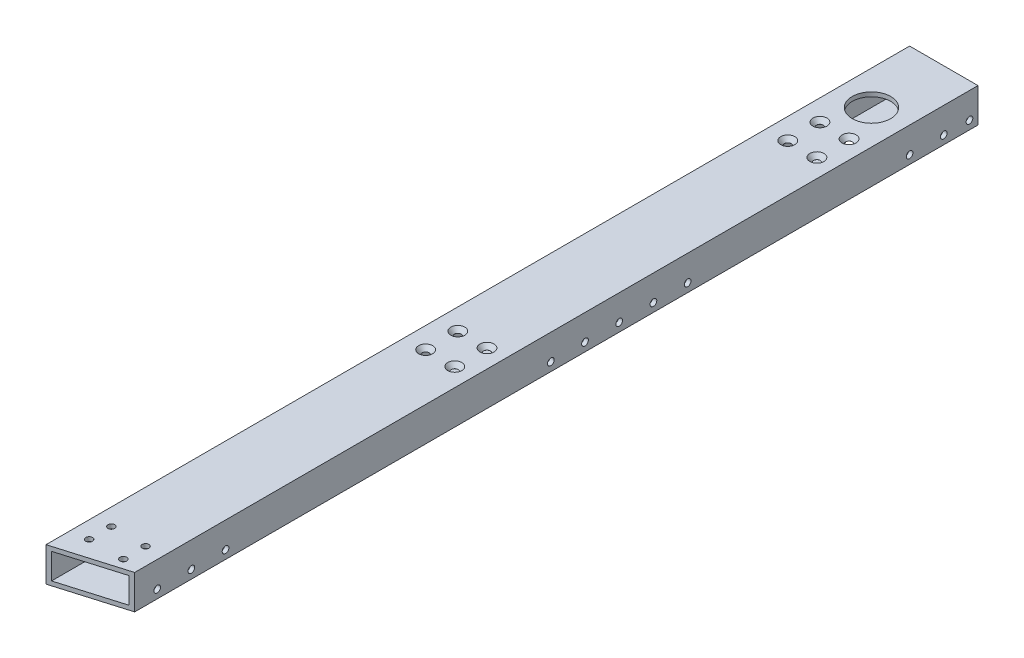
SolidWorks part; units mm, degrees
ref_plane "Front Plane" through (0, 0, 0) normal (0, 0, 1) x (1, 0, 0)
ref_plane "Top Plane" through (0, 0, 0) normal (0, 1, 0) x (1, 0, 0)
ref_plane "Right Plane" through (0, 0, 0) normal (1, 0, 0) x (0, 0, -1)
sketch "Sketch1" plane through (0, 0, 0) normal (0, 0, 1) x (1, 0, 0)
  line L0 (-22.225, 9.525) -> (22.225, 9.525)
  line L2 (-25.4, 12.7) -> (25.4, 12.7)
  line L3 (-25.4, 12.7) -> (-25.4, -12.7)
  line L4 (-25.4, -12.7) -> (25.4, -12.7)
  line L5 (25.4, 12.7) -> (25.4, -12.7)
  line L10 (22.225, 9.525) -> (22.225, -9.525)
  line L11 (-22.225, -9.525) -> (22.225, -9.525)
  line L12 (-22.225, 9.525) -> (-22.225, -9.525)
  point P12 (0, 12.7)
  point P14 (25.4, 0)
  dimension "Wall Thickness" = 3.175
  dimension "Outside Width" = 50.8
  dimension "Outside Height" = 25.4
  dimension "Inside Height" = 19.05
  dimension "Inside Width" = 44.45
sketch "Sketch2" plane through (0, 0, 0) normal (1, 0, 0) x (0, 0, -1)
  line L0 (320.675, 0) -> (-320.675, 0)
  point P4 (0, 0)
  point P7 (-320.675, 0)
  point P10 (320.675, 0)
  dimension "Length" = 641.35
sketch "Sketch3" plane through (0, 0, 0) normal (0, 0, 1) x (1, 0, 0)
  line L21 (25.4, 12.7) -> (-25.4, 12.7)
  line L22 (25.4, -12.7) -> (25.4, 12.7)
  line L23 (-25.4, -12.7) -> (25.4, -12.7)
  line L24 (-25.4, 12.7) -> (-25.4, -12.7)
  line L25 (25.4, 12.7) -> (-25.4, 12.7)
  line L26 (25.4, -12.7) -> (25.4, 12.7)
  line L27 (-25.4, -12.7) -> (25.4, -12.7)
  line L28 (-25.4, 12.7) -> (-25.4, -12.7)
  line L29 (22.225, 9.525) -> (-22.225, 9.525)
  line L30 (22.225, -9.525) -> (22.225, 9.525)
  line L31 (-22.225, -9.525) -> (22.225, -9.525)
  line L32 (-22.225, 9.525) -> (-22.225, -9.525)
  line L33 (22.225, 9.525) -> (-22.225, 9.525)
  line L34 (22.225, -9.525) -> (22.225, 9.525)
  line L35 (-22.225, -9.525) -> (22.225, -9.525)
  line L36 (-22.225, 9.525) -> (-22.225, -9.525)
  dimension "D1" = 0
  dimension "D2" = 0
extrude "Boss-Extrude1" add sketch "Sketch3" along normal up to vertex (320.675 mm away) and the other way up to vertex (320.675 mm away) up to point (0, 0, 320.675) other way up to point (0, 0, -320.675)
sketch "Drawing Reference" plane through (0, 0, 0) normal (1, 0, 0) x (0, 0, -1)
  line L0 (-320.675, 0) -> (320.675, 0) construction
  line L1 (0, -12.7) -> (0, 12.7) construction
  line L2 (-320.675, -12.7) -> (320.675, -12.7) construction
  line L5 (-320.675, 12.7) -> (320.675, 12.7) construction
  point P7 (-284.099, 0)
  point P8 (284.099, 0)
  dimension "D1" = 36.576
sketch "Sketch4" plane through (0, 12.7, 0) normal (0, 1, 0) x (1, 0, 0)
  line L0 (-25.4, -320.675) -> (25.4, -305.6274)
  line L1 (25.4, -320.675) -> (25.4, 320.675) construction
  line L2 (25.4, -320.675) -> (-25.4, -320.675)
  dimension "D1" = 16.5
extrude "Cut-Extrude1" cut sketch "Sketch4" against normal through all and the other way through all flip side to cut
sketch "Sketch8" plane through (0, 12.7, 0) normal (0, 1, 0) x (1, 0, 0)
  line L0 (0, 320.675) -> (0, 266.954) construction
  line L1 (25.4, 320.675) -> (-25.4, 320.675) construction
  circle A0 centre (0, 266.954) radius 14.2875
  dimension "D1" = 53.721
extrude "Cut-Extrude2" cut sketch "Sketch8" against normal through all
sketch "Sketch9" plane through (0, 12.7, 0) normal (0, 1, 0) x (1, 0, 0)
  line L0 (-12.7762, -284.753) -> (12.6238, -284.753) construction
  line L1 (12.6238, -284.753) -> (12.6238, -301.263) construction
  line L2 (12.6238, -301.263) -> (-12.7762, -301.263) construction
  line L3 (-12.7762, -301.263) -> (-12.7762, -284.753) construction
hole_wizard "#10 Clearance Hole1" positions "Sketch10" profile "Sketch11" hole size "#10" standard "ANSI Inch"
sketch "Sketch10" plane through (0, 12.7, 0) normal (0, 1, 0) x (1, 0, 0)
  point P0 (-12.7762, -284.753)
  point P3 (12.6238, -284.753)
  point P6 (12.6238, -301.263)
  point P9 (-12.7762, -301.263)
sketch "Sketch11" plane through (-12.7762, 12.7, 284.753) normal (1, 0, 0) x (0, 0, 1)
  line L0 (0, 0) -> (0, 6.5757)
  line L1 (0, 6.5757) -> (2.4892, 5.08)
  line L2 (2.4892, 5.08) -> (2.4892, 0)
  line L5 (2.4892, 0) -> (0, 0)
  line L10 (0, 6.5757) -> (-2.4892, 5.08) construction
  line L11 (0, -6.35) -> (0, 107.95) construction
  dimension "Hole Dia." = 4.9784
  dimension "Hole Depth" = 5.08
  dimension "Drill Angle" = 118
hole_wizard "#10 Clearance Hole2" positions "Sketch12" profile "Sketch13" hole size "#10" standard "ANSI Inch" end condition through all
sketch "Sketch12" plane through (25.4, 0, 0) normal (1, 0, 0) x (0, 0, -1)
  point P9 (3.429, -6.35)
  point P12 (28.829, -6.35)
  point P15 (54.229, -6.35)
  point P18 (79.629, -6.35)
  point P21 (105.029, -6.35)
  point P24 (-288.925, -6.35)
  point P27 (-263.525, -6.35)
  point P30 (-238.1261, -6.3882)
sketch "Sketch13" plane through (25.4, -6.35, -3.429) normal (0, 1, 0) x (0, 0, -1)
  line L0 (0, 0) -> (0, 50.8)
  line L1 (0, 50.8) -> (2.4892, 50.8)
  line L2 (2.4892, 50.8) -> (2.4892, 0)
  line L5 (2.4892, 0) -> (0, 0)
  line L11 (0, -6.35) -> (0, 107.95) construction
  dimension "Thru Hole Dia." = 4.9784
  dimension "Thru Hole Depth" = 50.8
hole_wizard "#10 Clearance Hole3" positions "Sketch14" profile "Sketch15" hole size "#10" standard "ANSI Inch"
sketch "Sketch14" plane through (25.4, 0, 0) normal (1, 0, 0) x (0, 0, -1)
  point P0 (269.875, -6.3882)
  point P3 (295.275, -6.3882)
  point P6 (314.325, -6.3882)
sketch "Sketch15" plane through (25.4, -6.3882, -269.875) normal (0, 1, 0) x (0, 0, -1)
  line L0 (0, 0) -> (0, 4.7977)
  line L1 (0, 4.7977) -> (2.4892, 3.302)
  line L2 (2.4892, 3.302) -> (2.4892, 0)
  line L5 (2.4892, 0) -> (0, 0)
  line L10 (0, 4.7977) -> (-2.4892, 3.302) construction
  line L11 (0, -6.35) -> (0, 107.95) construction
  dimension "Hole Dia." = 4.9784
  dimension "Hole Depth" = 3.302
  dimension "Drill Angle" = 118
sketch "Sketch16" plane through (0, -12.7, 0) normal (0, -1, 0) x (1, 0, 0)
  line L0 (0, -266.954) -> (12.752, -254.202) construction
hole_wizard "Tap Drill for #8-32 Tap1" positions "Sketch17" profile "Sketch18" hole size "#8-32" standard "ANSI Inch"
sketch "Sketch17" plane through (0, -12.7, 0) normal (0, -1, 0) x (-1, 0, 0)
  point P0 (-12.752, 254.202)
sketch "Sketch18" plane through (12.752, -12.7, -254.202) normal (1, 0, 0) x (0, 0, -1)
  line L0 (0, 0) -> (0, 6.1178)
  line L1 (0, 6.1178) -> (1.7272, 5.08)
  line L2 (1.7272, 5.08) -> (1.7272, 0)
  line L5 (1.7272, 0) -> (0, 0)
  line L10 (0, 6.1178) -> (-1.7272, 5.08) construction
  line L11 (0, -6.35) -> (0, 107.95) construction
  dimension "Hole Dia." = 3.4544
  dimension "Hole Depth" = 5.08
  dimension "Drill Angle" = 118
hole_wizard "#10 Clearance Hole4" positions "Sketch20" profile "Sketch21" hole size "#10" standard "ANSI Inch" end condition through all
sketch "Sketch20" plane through (0, -12.7, 0) normal (0, -1, 0) x (-1, 0, 0)
  point P0 (-11.8451, -30.4483)
  point P3 (9.7957, -30.4483)
  point P6 (9.7957, -54.3243)
  point P9 (-11.8451, -54.3243)
  point P12 (-11.8451, 214.5982)
  point P15 (9.7957, 214.5982)
  point P18 (-11.8451, 238.4742)
  point P21 (9.7957, 238.4742)
sketch "Sketch21" plane through (11.8451, -12.7, 30.4483) normal (1, 0, 0) x (0, 0, -1)
  line L0 (0, 0) -> (0, 25.4)
  line L1 (0, 25.4) -> (5.2197, 25.4)
  line L2 (2.4892, 22.2589) -> (2.4892, 0)
  line L5 (2.4892, 0) -> (0, 0)
  line L7 (5.2197, 25.4) -> (2.4892, 22.2589)
  line L8 (-5.2197, 25.4) -> (-2.4892, 22.2589) construction
  line L11 (0, -6.35) -> (0, 107.95) construction
  dimension "Thru Hole Dia." = 4.9784
  dimension "Thru Hole Depth" = 25.4
  dimension "Far C'Sink Dia." = 10.4394
  dimension "Far C'Sink Angle" = 82
equation "\"D1@Drawing Reference\"=\"Outside Width@Sketch1\" * 0.72"
